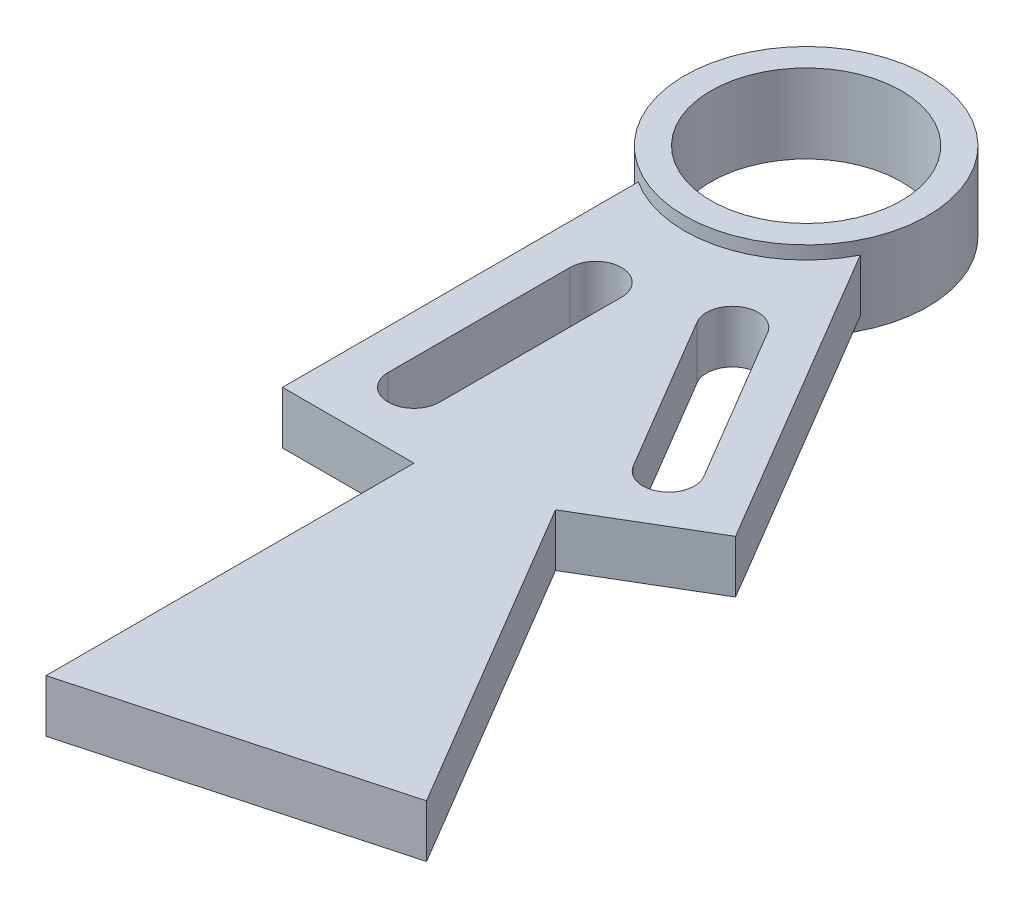
SolidWorks part; units mm, degrees
material "AISI 4130 Steel, annealed at 865C"
ref_plane "Front Plane" through (0, 0, 0) normal (0, 0, 1) x (1, 0, 0)
ref_plane "Top Plane" through (0, 0, 0) normal (0, 1, 0) x (1, 0, 0)
ref_plane "Right Plane" through (0, 0, 0) normal (1, 0, 0) x (0, 0, -1)
sketch "Sketch1" plane through (0, 0, 0) normal (0, 1, 0) x (1, 0, 0)
  line L0 (0, -50.4952) -> (0, -14.6812) construction
  line L1 (25.7368, -43.444) -> (7.4828, -12.6311) construction
  line L2 (0, -47.3837) -> (0, -25.4127) construction
  line L5 (-3.1115, -47.3837) -> (-3.1115, -25.4127)
  line L8 (-7.9375, -55.3212) -> (7.9375, -55.3212)
  line L9 (21.3674, -51.6418) -> (35.0256, -43.5505)
  line L10 (-7.9375, -55.3212) -> (-7.9375, -12.3505)
  line L11 (35.0256, -43.5505) -> (13.124, -6.5802)
  line L12 (7.9375, -55.3212) -> (7.9375, -99.7712)
  line L13 (21.3674, -51.6418) -> (44.023, -89.8848)
  line L14 (7.9375, -99.7712) -> (44.023, -89.8848)
  line L15 (0, -14.6812) -> (0, 0) construction
  line L16 (0, -55.3212) -> (0, -50.4952) construction
  line L17 (28.1965, -47.5961) -> (25.7368, -43.444)
  line L18 (3.1115, -47.3837) -> (3.1115, -25.4127)
  line L19 (12.9525, -21.8641) -> (24.1509, -40.767) construction
  line L20 (15.6295, -20.2782) -> (26.8279, -39.1811)
  line L21 (10.2755, -23.45) -> (21.4739, -42.3529)
  line L22 (7.4828, -12.6311) -> (0, 0) construction
  line L23 (0, 0) -> (20.1347, -73.4917) construction
  line L25 (178.1771, -300.7654) -> (14.7666, -24.9262) construction
  line L27 (0, 0) -> (25.9803, -94.828) construction
  circle A0 centre (0, 0) radius 11.5062
  circle A1 centre (0, 0) radius 14.6812
  arc A2 (-3.1115, -47.3837) -> (3.1115, -47.3837) centre (0, -47.3837) ccw
  arc A3 (3.1115, -25.4127) -> (-3.1115, -25.4127) centre (0, -25.4127) ccw
  arc A4 (15.6295, -20.2782) -> (10.2755, -23.45) centre (12.9525, -21.8641) ccw
  arc A5 (21.4739, -42.3529) -> (26.8279, -39.1811) centre (24.1509, -40.767) ccw
  point P9 (0, -36.3982)
  point P14 (18.5517, -31.3155)
  point P23 (0, -55.3212)
  point P26 (28.1965, -47.5961)
  point P33 (0, -50.4952)
  point P36 (25.7368, -43.444)
  point P38 (0, -22.3012)
  dimension "D2" = 29.3624
  dimension "D3" = 40.64
  dimension "D4" = 4.826
  dimension "D6" = 44.45
  dimension "D7" = 7.9375
  dimension "D5" = 4.826
  dimension "D8" = 7.62
  dimension "D9" = 76.2
extrude "Bearing extrude" add sketch "Sketch1" along normal mid plane 9.525 contours A1 A0 region at (-6.8368, 0, -12.521)
extrude "Boss-Extrude2" add sketch "Sketch1<5>" along normal mid plane 6.35 contours A1 L10 L8 L12 L14 L13 L9 L11 A4 A2 region at (15.3611, 0, 56.0678)
sketch "Sketch1<5>" plane through (0, 0, 0) normal (0, 1, 0) x (1, 0, 0) same geometry as "Sketch1"
sketch3d "Tab Point"
  line L0 (20.1347, 0, 73.4917) -> (20.1347, 23.7085, 73.4917) construction
  line L1 (0, 0, 0) -> (20.1347, 0, 73.4917) construction
  line L2 (0, 0, 0) -> (25.9803, 0, 94.828) construction
equation "\"Apex_thickness\"= .25"
equation "\"Bearing_diameter\"= .906"
equation "\"A-arm_angle\"= 32.91"
equation "\"D1@Sketch1\"=\"Bearing_diameter\""
equation "\"D1@Boss-Extrude2\"= \"Apex_thickness\""
equation "\"apex slot\"= 1.4"
equation "\"tube diameter\"= 5 / 8"
